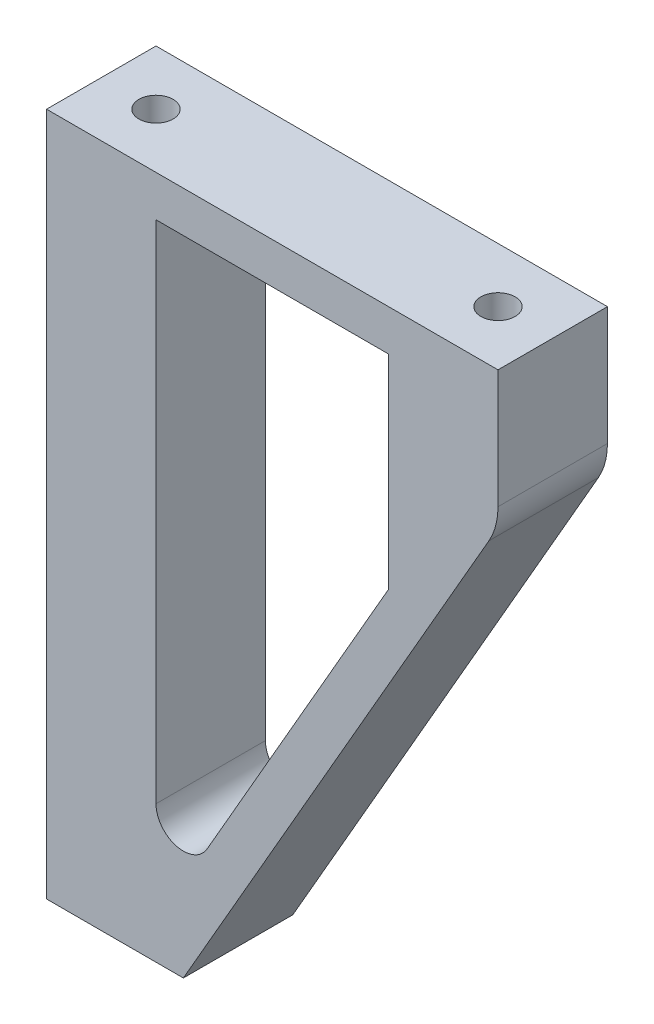
SolidWorks part; units mm, degrees
ref_plane "Спереди" through (0, 0, 0) normal (0, 0, 1) x (1, 0, 0)
ref_plane "Сверху" through (0, 0, 0) normal (0, 1, 0) x (1, 0, 0)
ref_plane "Справа" through (0, 0, 0) normal (1, 0, 0) x (0, 0, -1)
sketch "Эскиз1" plane through (0, 0, 0) normal (0, 0, 1) x (1, 0, 0)
  line L0 (-16.5, 25) -> (-16.5, -25)
  line L1 (-16.5, -25) -> (-6.5, -25)
  line L2 (-6.5, -25) -> (16.5, 15)
  line L3 (16.5, 15) -> (16.5, 25)
  line L4 (16.5, 25) -> (-16.5, 25)
  line L5 (-8.5, 22) -> (-8.5, -14.9693)
  line L7 (-4.7662, -15.9663) -> (8.5, 7.1054)
  line L8 (8.5, 7.1054) -> (8.5, 22)
  line L9 (8.5, 22) -> (-8.5, 22)
  line L10 (-12.5, 25) -> (-12.5, -25) construction
  line L11 (-8.5, 22) -> (-16.5, 22) construction
  line L12 (8.5, 22) -> (16.5, 22) construction
  line L13 (12.5, 25) -> (12.5, 8.0435) construction
  arc A0 (-8.5, -14.9693) -> (-4.7662, -15.9663) centre (-6.5, -14.9693) ccw
  point P1 (0, 25)
  point P6 (-16.5, 0)
  point P9 (0, 22)
  point P16 (-12.5, 22)
  point P22 (12.5, 22)
  dimension "D6" = 4
  dimension "D1" = 8
  dimension "D2" = 3
  dimension "D3" = 50
  dimension "D4" = 3
  dimension "D5" = 25
  dimension "D7" = 10
extrude "тело" add sketch "Эскиз1" along normal blind 8
fillet "Скругление1" [suppressed] radius 2
sketch "Эскиз6" plane through (0, 25, 0) normal (0, 1, 0) x (1, 0, 0)
  line L0 (16.5, -8) -> (-16.5, -8) construction
  line L1 (16.5, 0) -> (8.5, 0) construction
  line L2 (16.5, 0) -> (16.5, -8) construction
  line L3 (16.5, -8) -> (8.5, -8) construction
  line L4 (8.5, 0) -> (8.5, -8) construction
  line L5 (8.5, -4) -> (16.5, -4) construction
  circle A0 centre (12.5, -4) radius 1.25
  circle A1 centre (-12.5, -4) radius 1.25
  point P14 (-16, -4)
  point P15 (0, 0)
  dimension "D1" = 2.5
  dimension "D2" = 25
extrude "отверстие под шуруп сверху" cut sketch "Эскиз6" against normal blind 11
sketch "Эскиз5" plane through (0, -25, 0) normal (0, -1, 0) x (1, 0, 0)
  line L1 (-16.5, 8) -> (-16.5, 0) construction
  line L4 (-6.5, 8) -> (-6.5, 0) construction
  line L5 (-16.5, 4) -> (-6.5, 4) construction
  circle A0 centre (-12.5, 4) radius 1.25
  point P0 (-20, 4)
  point P4 (-26.0307, 3.1825)
  point P5 (-14, 4)
  point P14 (-10, 4)
  point P17 (-12, 8)
  dimension "D1" = 2.5
extrude "отверстие под шуруп снизу" cut sketch "Эскиз5" against normal blind 11
fillet "Скругление2" radius 5 1 edges at (16.5, 15, 4)
